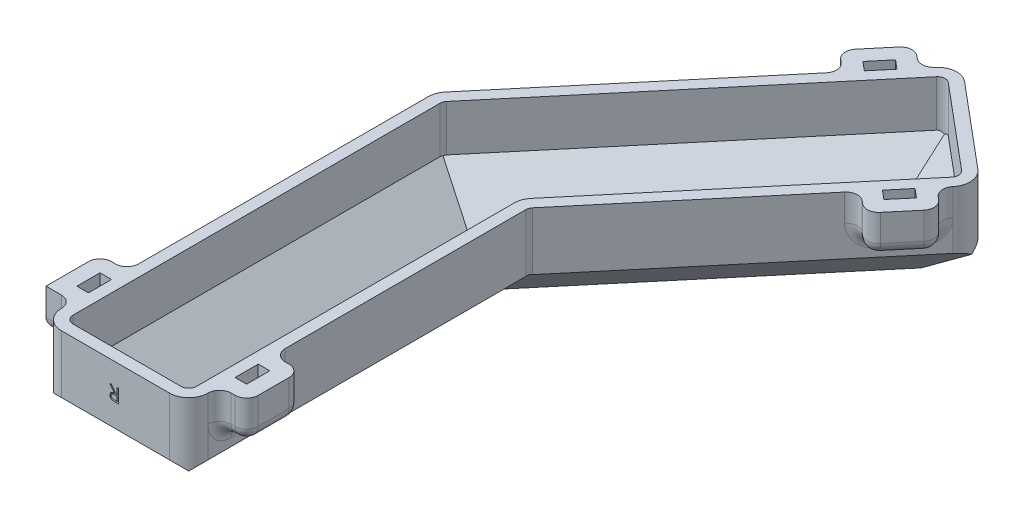
SolidWorks part; units mm, degrees
ref_plane "Front Plane" through (0, 0, 0) normal (0, 0, 1) x (1, 0, 0)
ref_plane "Top Plane" through (0, 0, 0) normal (0, 1, 0) x (1, 0, 0)
ref_plane "Right Plane" through (0, 0, 0) normal (1, 0, 0) x (0, 0, -1)
sketch "Sketch1" plane through (0, 0, 0) normal (0, 1, 0) x (1, 0, 0)
  line L0 (0, -95) -> (0, 0) construction
  line L1 (0, 0) -> (57.8509, 68.944) construction
  line L2 (19, -95) -> (19, -6.9154)
  line L3 (-19, -95) -> (-19, 6.9154)
  line L4 (-19, -95) -> (19, -95)
  line L5 (19, -6.9154) -> (72.4057, 56.731)
  line L6 (43.296, 81.157) -> (72.4057, 56.731)
  line L7 (43.296, 81.157) -> (-19, 6.9154)
  line L8 (43.6658, 76.9305) -> (68.1792, 56.3613) construction
  line L9 (43.6658, 76.9305) -> (-16, 5.8235) construction
  line L10 (-16, 5.8235) -> (-16, -92) construction
  line L11 (-16, -92) -> (16, -92) construction
  line L12 (16, -92) -> (16, -5.8235) construction
  line L13 (16, -5.8235) -> (68.1792, 56.3613) construction
  point P9 (0, -95)
  point P10 (57.8509, 68.944)
  point P12 (55.9225, 66.6459)
  point P13 (0, -92)
  dimension "D1" = 95
  dimension "D2" = 90
  dimension "D3" = 38
  dimension "D4" = 38
  dimension "D5" = 140
  dimension "D6" = 32
  dimension "D7" = 32
  dimension "D8" = 3
  dimension "D9" = 3
extrude "Boss-Extrude1" add sketch "Sketch1" along normal blind 25
sketch "Sketch2" plane through (0, 25, 0) normal (0, 1, 0) x (1, 0, 0)
  line L0 (43.6658, 76.9305) -> (68.1792, 56.3613)
  line L1 (43.6658, 76.9305) -> (-16, 5.8235)
  line L2 (-16, 5.8235) -> (-16, -92)
  line L3 (-16, -92) -> (16, -92)
  line L4 (16, -92) -> (16, -5.8235)
  line L5 (16, -5.8235) -> (68.1792, 56.3613)
  line L6 (0, 0) -> (57.8509, 68.944) construction
  line L7 (72.4057, 56.731) -> (43.296, 81.157) construction
  line L8 (0, 0) -> (0, -95) construction
  line L9 (-19, -95) -> (19, -95) construction
  point P0 (55.9225, 66.6459)
  point P1 (0, -92)
  dimension "D1" = 32
  dimension "D2" = 32
  dimension "D3" = 3
  dimension "D4" = 3
extrude "Cut-Extrude1" cut sketch "Sketch2" against normal blind 22
chamfer "Chamfer1" distance 10 angle 45 12 edges at (55.9225, 3, -66.6459) (42.0896, 3, -25.2689) (16, 3, 48.9118) (0, 3, 92) (-16, 3, 43.0882) (13.8329, 3, -41.377) (12.148, 0, -44.0362) (57.8509, 0, -68.944) (45.7029, 0, -24.9078) (19, 0, 50.9577) (-19, 0, 44.0423) (0, 0, 95)
fillet "Fillet1" radius 2 6 edges at (-16, 19, 92) (16, 19, 92) (-16, 19, -5.8235) (19, 17.5, 6.9154) (43.6658, 19, -76.9305) (68.1792, 19, -56.3613)
fillet "Fillet2" radius 5 6 edges at (-19, 17.5, 95) (19, 17.5, 95) (-19, 17.5, -6.9154) (16, 19, 5.8235) (72.4057, 17.5, -56.731) (43.296, 17.5, -81.157)
sketch "Sketch3" plane through (-14.5548, 0, -12.213) normal (-0.766, 0, -0.6428) x (-0.6428, 0, 0.766)
  line L0 (-85, 25) -> (5.0956, 25) construction
  line L1 (-68, 15) -> (-82, 15)
  line L2 (-68, 15) -> (-68, 25)
  line L3 (-68, 25) -> (-82, 25)
  line L4 (-82, 15) -> (-82, 25)
  line L5 (-68, 15) -> (-82, 25) construction
  line L6 (-68, 25) -> (-82, 15) construction
  line L7 (-85, 25) -> (-85, 10) construction
  point P0 (-75, 20)
  dimension "D1" = 10
  dimension "D2" = 14
  dimension "D3" = 3
sketch "Sketch4" plane through (14.5548, 0, 12.213) normal (0.766, 0, 0.6428) x (0.6428, 0, -0.766)
  line L0 (7.6434, 25) -> (85, 25) construction
  line L1 (82, 15) -> (68, 15)
  line L2 (82, 15) -> (82, 25)
  line L3 (82, 25) -> (68, 25)
  line L4 (68, 15) -> (68, 25)
  line L5 (82, 15) -> (68, 25) construction
  line L6 (82, 25) -> (68, 15) construction
  line L7 (85, 10) -> (85, 25) construction
  point P0 (75, 20)
  dimension "D1" = 3
  dimension "D2" = 10
  dimension "D3" = 14
sketch "Sketch6" plane through (-19, 0, 0) normal (-1, 0, 0) x (0, 0, 1)
  line L0 (-5.0956, 25) -> (90, 25) construction
  line L1 (87, 15) -> (73, 15)
  line L2 (87, 15) -> (87, 25)
  line L3 (87, 25) -> (73, 25)
  line L4 (73, 15) -> (73, 25)
  line L5 (87, 15) -> (73, 25) construction
  line L6 (87, 25) -> (73, 15) construction
  line L7 (90, 10) -> (90, 25) construction
  point P0 (80, 20)
  dimension "D1" = 3
  dimension "D2" = 14
  dimension "D3" = 10
sketch "Sketch7" plane through (19, 0, 0) normal (1, 0, 0) x (0, 0, -1)
  line L0 (-90, 25) -> (-7.6434, 25) construction
  line L1 (-73, 15) -> (-87, 15)
  line L2 (-73, 15) -> (-73, 25)
  line L3 (-73, 25) -> (-87, 25)
  line L4 (-87, 15) -> (-87, 25)
  line L5 (-73, 15) -> (-87, 25) construction
  line L6 (-73, 25) -> (-87, 15) construction
  line L7 (-90, 25) -> (-90, 10) construction
  point P0 (-80, 20)
  dimension "D1" = 10
  dimension "D2" = 14
  dimension "D3" = 3
sketch "Sketch9" plane through (0, 0, 95) normal (0, 0, 1) x (1, 0, 0)
  line L0 (0, 10) -> (0, 25) construction
  line L1 (-14, 10) -> (14, 10) construction
  line L2 (-14, 25) -> (14, 25) construction
  line L3 (14, 17.5) -> (-14, 17.5) construction
  line L4 (14, 10) -> (14, 25) construction
  line L5 (-14, 25) -> (-14, 10) construction
  text T0 "<r180>R</r>"
extrude "Cut-Extrude4" cut sketch "Sketch9" against normal blind 0.5
extrude "Boss-Extrude2" add sketch "Sketch3" along normal blind 7
extrude "Boss-Extrude3" add sketch "Sketch7" along normal blind 7
extrude "Boss-Extrude4" add sketch "Sketch6" along normal blind 7
extrude "Boss-Extrude5" add sketch "Sketch4" along normal blind 7
sketch "Sketch11" plane through (0, 25, 0) normal (0, 1, 0) x (1, 0, 0)
  line L0 (33.2845, 73.8928) -> (35.5826, 71.9644)
  line L1 (-22, -83) -> (-19, -83)
  line L2 (-22, -83) -> (-22, -77)
  line L3 (-22, -77) -> (-19, -77)
  line L4 (-19, -83) -> (-19, -77)
  line L5 (19, -77) -> (22, -77)
  line L6 (19, -77) -> (19, -83)
  line L7 (19, -83) -> (22, -83)
  line L8 (22, -77) -> (22, -83)
  line L9 (33.2845, 73.8928) -> (29.4277, 69.2965)
  line L10 (35.5826, 71.9644) -> (31.7259, 67.3682)
  line L11 (29.4277, 69.2965) -> (31.7259, 67.3682)
  line L12 (64.6923, 47.5385) -> (66.9904, 45.6101)
  line L13 (64.6923, 47.5385) -> (60.8356, 42.9422)
  line L14 (66.9904, 45.6101) -> (63.1337, 41.0139)
  line L15 (60.8356, 42.9422) -> (63.1337, 41.0139)
  line L16 (72.6257, 46.1032) -> (67.2634, 50.6027) construction
  line L17 (67.2634, 50.6027) -> (69.1918, 52.9008) construction
  line L18 (32.7914, 79.5281) -> (38.1537, 75.0286) construction
  line L19 (40.0821, 77.3267) -> (38.1537, 75.0286) construction
  line L21 (-19, 5.0956) -> (-19, -73) construction
  line L22 (19, -73) -> (19, -7.6434) construction
  line L23 (-26, -73) -> (-19, -73) construction
  dimension "D1" = 4
  dimension "D2" = 4
  dimension "D3" = 6
  dimension "D4" = 3
extrude "Cut-Extrude5" cut sketch "Sketch11" against normal through all
fillet "Fillet3" radius 3 35 edges at (-19, 20, 87) (-19, 20, 73) (19, 20, 87) (19, 20, 73) (58.2644, 20, -39.8781) (-22.5, 15, 87) (-19, 15, 85) (-26, 20, 73) (-26, 15, 80) (-19, 15, 75) (-22.5, 15, 73) (26, 20, 87) (22.5, 15, 87) (19, 15, 85) (19, 15, 75) (26, 15, 80) (26, 20, 73) (22.5, 15, 73) (63.6267, 20, -35.3785) (59.55, 15, -41.4101) (60.9456, 15, -37.6283) (68.1262, 15, -40.7409) (72.6257, 20, -46.1032) (69.9446, 15, -48.3529) (65.9779, 15, -49.0706) (67.2634, 20, -50.6027) (29.1547, 20, -64.304) (38.1537, 20, -75.0286) (30.4403, 15, -65.8361) (26.4736, 15, -66.5537) (23.7924, 20, -68.8035) (32.7914, 20, -79.5281) (28.2919, 15, -74.1658) (35.4726, 15, -77.2784) (36.8682, 15, -73.4965)
